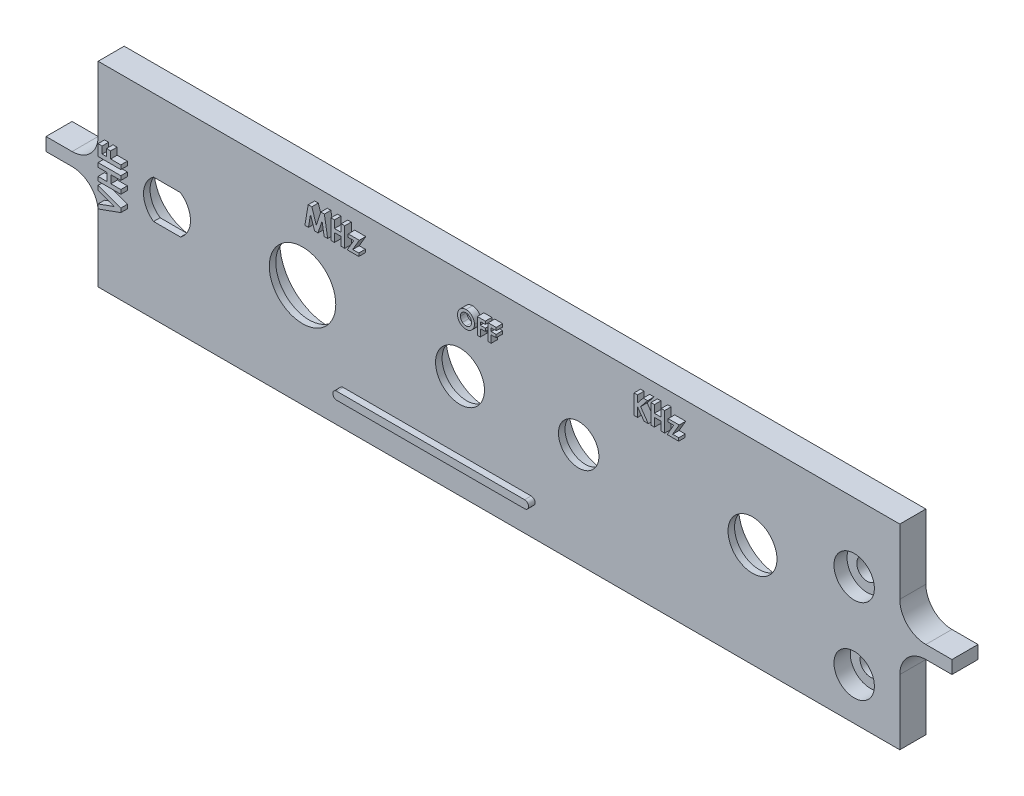
SolidWorks part; units mm, degrees
ref_plane "Front Plane" through (0, 0, 0) normal (0, 0, 1) x (1, 0, 0)
ref_plane "Top Plane" through (0, 0, 0) normal (0, 1, 0) x (1, 0, 0)
ref_plane "Right Plane" through (0, 0, 0) normal (1, 0, 0) x (0, 0, -1)
sketch "Sketch1" plane through (0, 0, 0) normal (0, 0, 1) x (1, 0, 0)
  line L0 (16.5053, 12.9565) -> (20.632, 12.9565) construction
  line L1 (8, 0) -> (131, 0)
  line L2 (0, 14) -> (0, 16)
  line L3 (8, 30) -> (131, 30)
  line L4 (139, 14) -> (139, 16)
  line L5 (69.5, 30) -> (69.5, 0) construction
  line L6 (20.632, 18.8565) -> (16.5053, 18.8565) construction
  line L11 (16.5053, 12.9565) -> (20.632, 12.9565)
  line L12 (20.632, 18.8565) -> (16.5053, 18.8565)
  line L13 (8, 30) -> (8, 20)
  line L14 (4, 16) -> (0, 16)
  line L15 (8, 0) -> (8, 10)
  line L16 (4, 14) -> (0, 14)
  line L17 (131, 30) -> (131, 20)
  line L18 (135, 16) -> (139, 16)
  line L19 (131, 0) -> (131, 10)
  line L20 (135, 14) -> (139, 14)
  line L21 (0, 15) -> (139, 15) construction
  line L22 (0, 0) -> (131, 0) construction
  line L23 (0, 0) -> (0, 64.6609) construction
  arc A8 (8, 10) -> (4, 14) centre (4, 10) ccw
  arc A9 (8, 20) -> (4, 16) centre (4, 20) cw
  arc A11 (131, 10) -> (135, 14) centre (135, 10) cw
  arc A12 (131, 20) -> (135, 16) centre (135, 20) ccw
  circle A13 centre (124, 19.5) radius 1.6 construction
  circle A14 centre (108.3997, 15.9065) radius 3.75 construction
  circle A15 centre (81.7309, 15.9065) radius 3.1 construction
  circle A16 centre (63.5225, 15.9065) radius 3.75 construction
  circle A17 centre (39.3612, 15.9065) radius 5.1 construction
  arc A18 (16.5053, 18.8565) -> (16.5053, 12.9565) centre (18.5687, 15.9065) ccw construction
  arc A19 (20.632, 12.9565) -> (20.632, 18.8565) centre (18.5687, 15.9065) ccw construction
  circle A20 centre (124, 19.5) radius 1.6
  circle A21 centre (108.3997, 15.9065) radius 3.75
  circle A22 centre (81.7309, 15.9065) radius 3.1
  circle A23 centre (63.5225, 15.9065) radius 3.75
  circle A24 centre (39.3612, 15.9065) radius 5.1
  arc A25 (16.5053, 18.8565) -> (16.5053, 12.9565) centre (18.5687, 15.9065) ccw
  arc A26 (20.632, 12.9565) -> (20.632, 18.8565) centre (18.5687, 15.9065) ccw
  circle A27 centre (124, 6.5) radius 1.6
  point P21 (131, 14)
  point P25 (8, 16)
  point P40 (131, 16)
  dimension "D3" = 13
  dimension "D8" = 4
  dimension "D12" = 4
  dimension "D11" = 8
  dimension "D15" = 123
  dimension "D16" = 139
  dimension "D20" = 30
  dimension "D21" = 14
  dimension "D22" = 8
  dimension "D9" = 8
  dimension "D10" = 14
extrude "Boss-Extrude1" add sketch "Sketch1" along normal blind 4
sketch "Sketch4" plane through (0, 0, 4) normal (0, 0, 1) x (1, 0, 0)
  line L0 (12.4839, 20.2661) -> (12.4839, 6.4719) construction
  line L1 (45.6117, 4.8536) -> (74.4421, 4.8536) construction
  line L2 (33.1689, 25.0481) -> (113.2155, 25.0481) construction
  line L3 (45.6117, 4.2536) -> (74.4421, 4.2536)
  line L4 (45.6117, 5.4536) -> (74.4421, 5.4536)
  arc A0 (45.6117, 4.2536) -> (45.6117, 5.4536) centre (45.6117, 4.8536) cw
  arc A1 (74.4421, 4.2536) -> (74.4421, 5.4536) centre (74.4421, 4.8536) ccw
  text T0 "VHF" font "Century Gothic" height 3.5
  text T1 "<b>OFF</b>" font "Century Gothic" height 2.5
  text T5 "MHz" font "Century Gothic" height 3
  text T6 "KHz" font "Century Gothic" height 3
  dimension "D1" = 0.6
  dimension "D2" = 0.6
extrude "Textos" add sketch "Sketch4" along normal blind 1
sketch "Sketch5" plane through (0, 0, 0) normal (0, 0, -1) x (-1, 0, 0)
  arc A0 (-20.632, 18.8565) -> (-20.632, 12.9565) centre (-18.5687, 15.9065) ccw construction
  circle A1 centre (-108.3997, 15.9065) radius 3.75 construction
  circle A2 centre (-81.7309, 15.9065) radius 3.1 construction
  circle A3 centre (-63.5225, 15.9065) radius 3.75 construction
  circle A4 centre (-39.3612, 15.9065) radius 5.1 construction
  circle A5 centre (-18.5687, 15.9065) radius 3.6 construction
  circle A6 centre (-39.3612, 15.9065) radius 5.1 construction
  circle A7 centre (-63.5225, 15.9065) radius 3.75 construction
  circle A8 centre (-81.7309, 15.9065) radius 3.1 construction
  circle A9 centre (-108.3997, 15.9065) radius 3.75 construction
  circle A10 centre (-18.5687, 15.9065) radius 6
  circle A11 centre (-39.3612, 15.9065) radius 7.5
  circle A12 centre (-63.5225, 15.9065) radius 6.15
  circle A13 centre (-81.7309, 15.9065) radius 5.5
  circle A14 centre (-108.3997, 15.9065) radius 6.15
  dimension "D2" = 12
  dimension "D3" = 15
  dimension "D4" = 12.3
  dimension "D5" = 11
  dimension "D6" = 12.3
  dimension "D1" = 2.4
extrude "Cut-Extrude1" cut sketch "Sketch5" against normal blind 3
sketch "Sketch6" plane through (0, 0, 4) normal (0, 0, 1) x (1, 0, 0)
  circle A0 centre (124, 19.5) radius 1.6 construction
  circle A1 centre (124, 19.5) radius 1.6 construction
  circle A2 centre (124, 19.5) radius 3.1
  circle A3 centre (124, 19.5) radius 0.1
  circle A4 centre (124, 6.5) radius 1.6 construction
  circle A5 centre (124, 6.5) radius 1.6 construction
  circle A6 centre (124, 6.5) radius 3.1
  circle A7 centre (124, 6.5) radius 0.1
  dimension "D1" = 1.5
  dimension "D2" = 1.5
  dimension "D3" = 1.5
  dimension "D4" = 1.5
extrude "Cut-Extrude2" cut sketch "Sketch6" against normal blind 2 contours A2
extrude "Cut-Extrude3" cut sketch "Sketch6<3>" against normal blind 2.5 contours A6 A7 region at (120.9877, 6.5, 4)
sketch "Sketch6<3>" plane through (0, 0, 4) normal (0, 0, 1) x (1, 0, 0) same geometry as "Sketch6"
